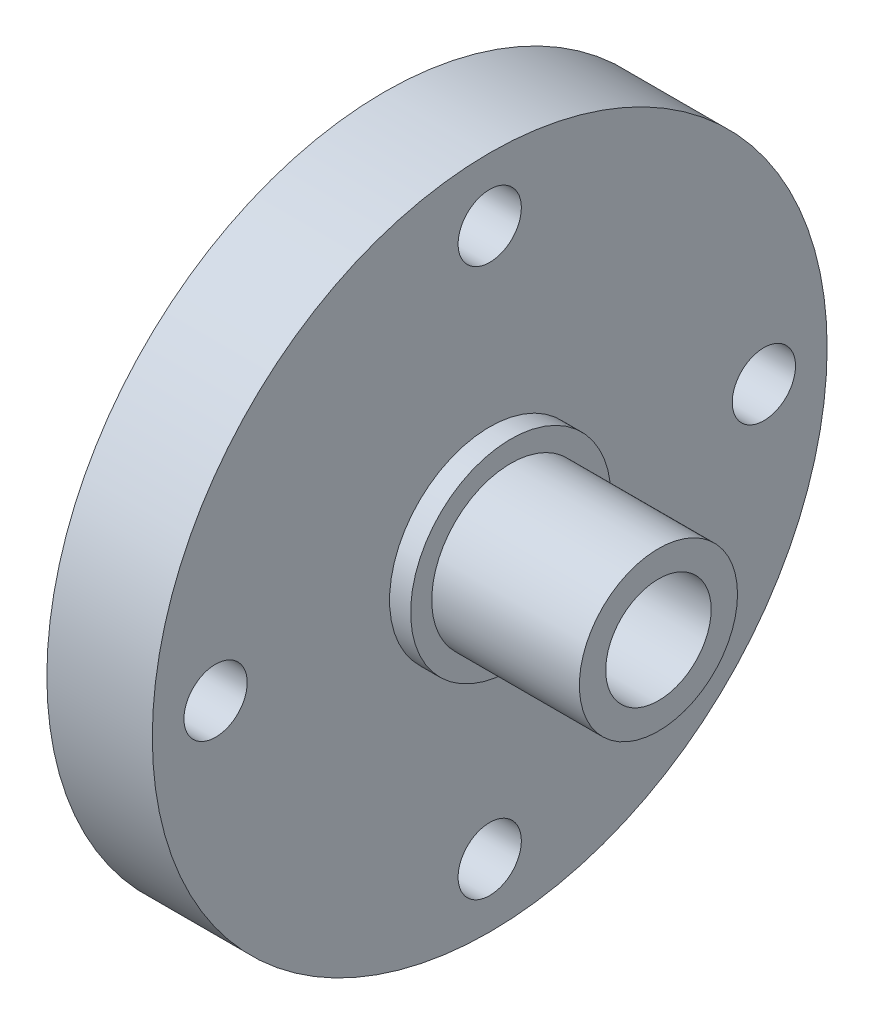
SolidWorks part; units mm, degrees
ref_plane "Front Plane" through (0, 0, 0) normal (0, 0, 1) x (1, 0, 0)
ref_plane "Top Plane" through (0, 0, 0) normal (0, 1, 0) x (1, 0, 0)
ref_plane "Right Plane" through (0, 0, 0) normal (1, 0, 0) x (0, 0, -1)
sketch "Sketch1" plane through (0, 0, 0) normal (1, 0, 0) x (0, 0, -1)
  circle A0 centre (0, 0) radius 16
  circle A1 centre (0, 0) radius 2.5
  dimension "D1" = 5
  dimension "D2" = 32
extrude "Boss-Extrude1" add sketch "Sketch1" along normal blind 5
sketch "Sketch2" plane through (5, 0, 0) normal (1, 0, 0) x (0, 0, -1)
  circle A0 centre (0, 13) radius 1.5
  circle A1 centre (0, 0) radius 2.5 construction
  circle A7 centre (13, 0) radius 1.5
  circle A8 centre (0, -13) radius 1.5
  circle A9 centre (-13, 0) radius 1.5
  point P13 (0, 0)
  point P17 (0, 0)
  dimension "D1" = 13
  dimension "D2" = 3
extrude "Cut-Extrude1" cut sketch "Sketch2" against normal through all
sketch "Sketch4" plane through (5, 0, 0) normal (1, 0, 0) x (0, 0, -1)
  circle A0 centre (0, 0) radius 2.5 construction
  circle A1 centre (0, 0) radius 2.5
  circle A2 centre (0, 0) radius 4.75
  dimension "D1" = 9.5
extrude "Boss-Extrude2" add sketch "Sketch4" along normal blind 1
sketch "Sketch5" plane through (6, 0, 0) normal (1, 0, 0) x (0, 0, -1)
  circle A0 centre (0, 0) radius 2.5 construction
  circle A1 centre (0, 0) radius 2.5
  circle A2 centre (0, 0) radius 3.75
  dimension "D1" = 7.5
extrude "Boss-Extrude3" add sketch "Sketch5" along normal blind 7
